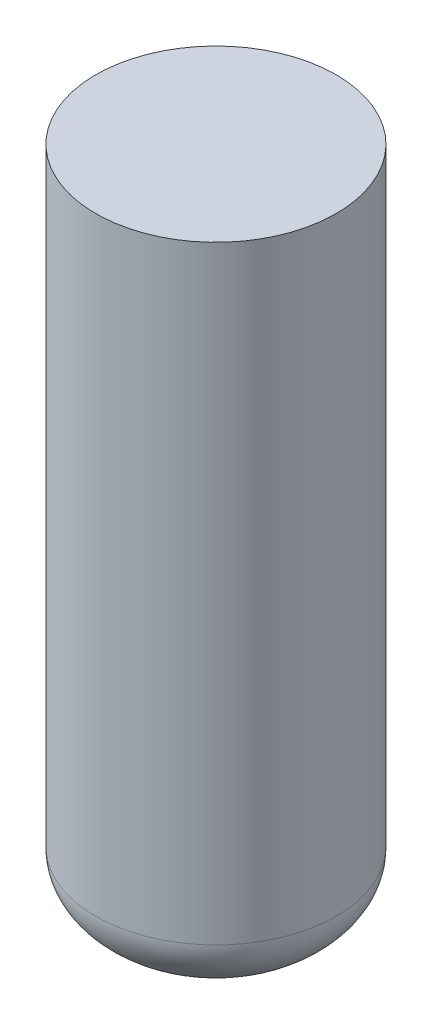
SolidWorks part; units mm, degrees
material "Liquid Oxygen"
ref_plane "Front Plane" through (0, 0, 0) normal (0, 0, 1) x (1, 0, 0)
ref_plane "Top Plane" through (0, 0, 0) normal (0, 1, 0) x (1, 0, 0)
ref_plane "Right Plane" through (0, 0, 0) normal (1, 0, 0) x (0, 0, -1)
sketch "Sketch1" plane through (0, 0, 0) normal (0, 1, 0) x (1, 0, 0)
  circle A0 centre (0, 0) radius 95.25
  dimension "D1" = 190.5
extrude "Boss-Extrude1" add sketch "Sketch1" along normal blind 482.6
sketch "Sketch2" plane through (0, 0, 0) normal (1, 0, 0) x (0, 0, -1)
  line L0 (95.25, 482.6) -> (-95.25, 482.6) construction
  line L1 (0, 544.576) -> (0, 482.6)
  line L2 (0, 482.6) -> (95.25, 482.6)
  ellipse E0 centre (0, 482.6) end of major axis (95.25, 482.6) minor radius 61.976 (95.25, 482.6) -> (0, 544.576) ccw
  dimension "D1" = 61.976
revolve "Revolve1" add sketch "Sketch2" angle 360 about L1
sketch "Sketch3" plane through (0, 0, 0) normal (1, 0, 0) x (0, 0, -1)
  line L0 (0, -59.69) -> (0, 0)
  line L1 (0, 0) -> (95.25, 0)
  ellipse E0 centre (0, 0) end of major axis (95.25, 0) minor radius 59.69 (0, -59.69) -> (95.25, 0) ccw
  dimension "D1" = 59.69
revolve "Revolve2" add sketch "Sketch3" angle 360 about L0
ref_plane "Plane1" through (0, 544.576, 0) normal (0, 1, 0) x (1, 0, 0)
sketch "Sketch4" plane through (0, 544.576, 0) normal (0, 1, 0) x (1, 0, 0)
  circle A0 centre (0, 0) radius 95.25
extrude "7 Percent Ullage" cut sketch "Sketch4" against normal blind 62.484
